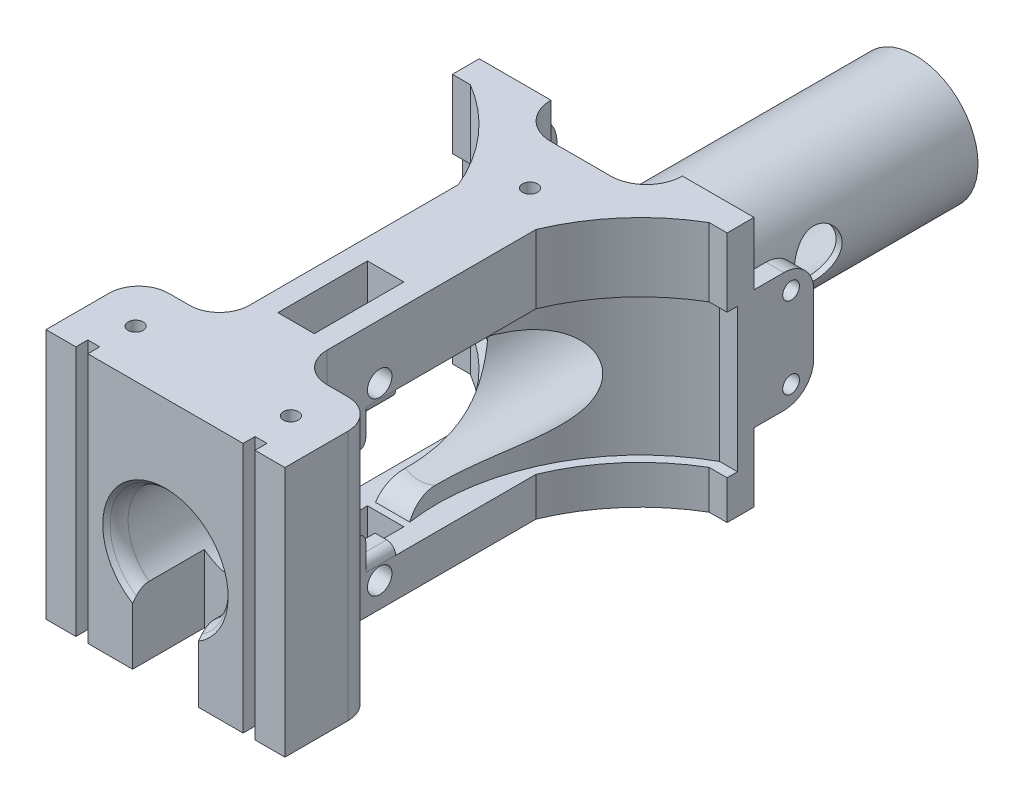
SolidWorks part; units mm, degrees
ref_plane "前视基准面" through (0, 0, 0) normal (0, 0, 1) x (1, 0, 0)
ref_plane "上视基准面" through (0, 0, 0) normal (0, 1, 0) x (1, 0, 0)
ref_plane "右视基准面" through (0, 0, 0) normal (1, 0, 0) x (0, 0, -1)
sketch "草图1" plane through (0, 0, 0) normal (0, 0, 1) x (1, 0, 0)
  line L1 (-20, 23.5) -> (20, 23.5)
  line L2 (-20, 23.5) -> (-20, -23.5)
  line L3 (-20, -23.5) -> (20, -23.5)
  line L4 (20, 23.5) -> (20, -23.5)
  line L5 (-20, 23.5) -> (20, -23.5) construction
  line L6 (-20, -23.5) -> (20, 23.5) construction
  point P0 (0, 0)
  dimension "D1" = 47
  dimension "D2" = 40
extrude "凸台-拉伸1" add sketch "草图1" along normal mid plane 65
sketch "草图2" plane through (0, 23.5, 0) normal (0, 1, 0) x (1, 0, 0)
  line L0 (-36.5, 0) -> (36.5, 0) construction
  line L1 (21.9876, 29.0799) -> (51.0124, 29.0799)
  line L2 (6.5, -27.5) -> (6.5, 12.5)
  line L4 (-6.5, 12.5) -> (-6.5, -27.5)
  line L5 (20, -32.5) -> (-20, -32.5) construction
  line L6 (-51.5217, -27.5) -> (-6.5, -27.5)
  line L8 (-48.1731, 29.0799) -> (-21.9876, 29.0799)
  line L9 (6.5, -27.5) -> (53.8205, -27.5)
  circle A0 centre (36.5, 0) radius 30 construction
  circle A1 centre (-36.5, 0) radius 30 construction
  arc A2 (21.9876, 29.0799) -> (6.5, 12.5) centre (36.5, 0) ccw
  arc A3 (-48.1731, 29.0799) -> (-51.5217, -27.5) centre (-36.5, 0) ccw
  arc A4 (53.8205, -27.5) -> (51.0124, 29.0799) centre (36.5, 0) ccw
  arc A5 (-6.5, 12.5) -> (-21.9876, 29.0799) centre (-36.5, 0) ccw
  point P3 (0, 0)
  dimension "D2" = 60
  dimension "D3" = 65
  dimension "D1" = 73
  dimension "D4" = 5
extrude "切除-拉伸1" cut sketch "草图2" against normal through all
sketch "草图3" plane through (0, 0, 32.5) normal (0, 0, 1) x (1, 0, 0)
  circle A0 centre (0, 0) radius 9
  dimension "D1" = 18
extrude "切除-拉伸2" cut sketch "草图3" against normal through all
sketch "草图4" plane through (0, 0, 0) normal (0, 1, 0) x (1, 0, 0)
  line L1 (56.4937, -27.5) -> (16.5063, -27.5)
  line L2 (-20, -27.5) -> (-6.5, -27.5) construction
  line L3 (52.5, 30) -> (20.5, 30)
  line L5 (-20.5, 30) -> (-52.5, 30)
  line L6 (-16.5063, -27.5) -> (-56.4937, -27.5)
  arc A1 (56.4937, -27.5) -> (52.5, 30) centre (36.5, 0) ccw
  arc A2 (-52.5, 30) -> (-56.4937, -27.5) centre (-36.5, 0) ccw
  arc A3 (-16.5063, -27.5) -> (-20.5, 30) centre (-36.5, 0) ccw
  arc A4 (20.5, 30) -> (16.5063, -27.5) centre (36.5, 0) ccw
  point P8 (36.5, 0)
  point P12 (-36.5, 0)
  dimension "D2" = 34
  dimension "D3" = 34
  dimension "D1" = 73
  dimension "D4" = 36.5
  dimension "D5" = 30
extrude "切除-拉伸3" cut sketch "草图4" against normal mid plane 24
sketch "草图7" plane through (-6.5, 0, 0) normal (-1, 0, 0) x (0, 0, 1)
  circle A1 centre (13.6704, 14.3) radius 2.05
  dimension "D1" = 13.6704
  dimension "D2" = 4.1
  dimension "D3" = 13.6704
  dimension "D4" = 14.3
extrude "切除-拉伸5" cut sketch "草图7" against normal through all
mirror "镜向1" about plane through (0, 0, 0) normal (0, 1, 0) of "切除-拉伸5"
sketch "草图9" plane through (6.5, 0, 0) normal (1, 0, 0) x (0, 0, -1)
  line L0 (-16, -12) -> (12.5, -12) construction
  line L1 (-16, 12) -> (-5, 12)
  line L2 (-16, 12) -> (-16, -12)
  line L3 (-16, -12) -> (-5, -12)
  line L4 (-5, 12) -> (-5, -12)
  line L5 (29.7279, -12) -> (-16, -12) construction
  dimension "D1" = 11
extrude "切除-拉伸7" cut sketch "草图9" against normal through all
sketch "草图10" plane through (0, 0, -32.5) normal (0, 0, -1) x (-1, 0, 0)
  circle A0 centre (0, 0) radius 9.5
  dimension "D1" = 19
extrude "切除-拉伸8" cut sketch "草图10" against normal up to next
sketch "草图12" plane through (0, 23.5, 0) normal (0, 1, 0) x (1, 0, 0)
  line L0 (20, -32.5) -> (-20, -32.5) construction
  line L1 (-3.05, -6.17) -> (3.05, -6.17)
  line L2 (-3.05, -6.17) -> (-3.05, -21.17)
  line L3 (-3.05, -21.17) -> (3.05, -21.17)
  line L4 (3.05, -6.17) -> (3.05, -21.17)
  line L5 (-3.05, -6.17) -> (3.05, -21.17) construction
  line L6 (-3.05, -21.17) -> (3.05, -6.17) construction
  point P0 (0, -13.67)
  dimension "D1" = 18.83
  dimension "D2" = 15
  dimension "D3" = 6.1
extrude "切除-拉伸9" cut sketch "草图12" against normal through all
fillet "圆角4" radius 1 4 edges at (-4.9049, 7.546, 16) (4.9049, 7.546, 16) (4.9049, -7.546, 16) (-4.9049, -7.546, 16)
fillet "圆角5" radius 5 2 edges at (0, -9.5, 5) (0, 9.5, 5)
sketch "草图13" plane through (0, 0, 32.5) normal (0, 0, 1) x (1, 0, 0)
  line L4 (20, -23.5) -> (20, 23.5)
  line L5 (20, 23.5) -> (-20, 23.5)
  line L6 (-20, 23.5) -> (-20, -23.5)
  line L7 (-20, -23.5) -> (20, -23.5)
  line L8 (20, -23.5) -> (20, 23.5)
  line L9 (20, 23.5) -> (-20, 23.5)
  line L10 (-20, 23.5) -> (-20, -23.5)
  line L11 (-20, -23.5) -> (20, -23.5)
  circle A0 centre (0, 0) radius 9 construction
  circle A1 centre (0, 0) radius 9
  dimension "D1" = 0
extrude "凸台-拉伸2" add sketch "草图13" along normal blind 10.54
sketch "草图14" plane through (0, 0, 43.04) normal (0, 0, 1) x (1, 0, 0)
  line L0 (0, 0) -> (0, 30.6084) construction
  line L1 (14, -23.5) -> (14, 23.5) construction
  line L4 (15, -23.5) -> (15, 23.5)
  line L6 (13, -23.5) -> (13, 23.5)
  line L7 (13, 23.5) -> (15, 23.5)
  line L8 (20, 23.5) -> (-20, 23.5) construction
  line L9 (13, -23.5) -> (15, -23.5)
  line L10 (-20, -23.5) -> (20, -23.5) construction
  line L13 (15, 0) -> (15, 30.6084) construction
  line L14 (14, 0) -> (14, 30.6084) construction
  line L15 (13, 0) -> (13, 30.6084) construction
  dimension "D2" = 2
  dimension "D3" = 1
  dimension "D1" = 14
extrude "切除-拉伸10" cut sketch "草图14" against normal blind 2
mirror "镜向2" about plane through (0, 0, 0) normal (1, 0, 0) of "切除-拉伸10"
sketch "草图15" plane through (0, 0, 43.04) normal (0, 0, 1) x (1, 0, 0)
  line L0 (-20, -23.5) -> (-15, -23.5) construction
  line L1 (-20, -23.5) -> (20, -23.5)
  line L2 (-20, -23.5) -> (-20, -18.7)
  line L3 (-20, -18.7) -> (20, -18.7)
  line L4 (20, -23.5) -> (20, -18.7)
  line L5 (-20, 23.5) -> (-20, -23.5) construction
  line L6 (20, -23.5) -> (20, 23.5) construction
  dimension "D1" = 4.8
extrude "切除-拉伸11" cut sketch "草图15" against normal through all
sketch "草图16" plane through (0, -18.7, 0) normal (0, -1, 0) x (1, 0, 0)
  line L0 (13, 43.04) -> (-13, 43.04) construction
  line L1 (-5.5, 43.04) -> (5.5, 43.04)
  line L2 (-5.5, 43.04) -> (-5.5, 31.04)
  line L3 (-5.5, 31.04) -> (5.5, 31.04)
  line L4 (5.5, 43.04) -> (5.5, 31.04)
  line L5 (-5.5, 43.04) -> (5.5, 31.04) construction
  line L6 (-5.5, 31.04) -> (5.5, 43.04) construction
  point P0 (0, 37.04)
  dimension "D1" = 11
  dimension "D2" = 12
extrude "切除-拉伸12" cut sketch "草图16" against normal up to surface (11.5761 mm away) up to face at (0, 0, 20.6675)
sketch "草图17" plane through (0, -18.7, 0) normal (0, -1, 0) x (1, 0, 0)
  line L0 (10, 37.04) -> (-10, 37.04) construction
  line L2 (9, 43.04) -> (-9, 43.04) construction
  circle A0 centre (-10, 37.04) radius 1.25
  circle A1 centre (10, 37.04) radius 1.25
  point P2 (0, 37.04)
  dimension "D3" = 2.5
  dimension "D1" = 20
  dimension "D2" = 6
extrude "切除-拉伸13" cut sketch "草图17" against normal blind 15
cosmetic thread "装饰螺纹线5" parameters "D2"=3
cosmetic thread "装饰螺纹线6" parameters "D2"=3
sketch "草图18" plane through (0, 0, 43.04) normal (0, 0, 1) x (1, 0, 0)
  line L0 (0, 0) -> (0, -18.7) construction
  line L1 (-5.5, -18.7) -> (5.5, -18.7) construction
  line L3 (6.5, -12) -> (13.5, -12)
  line L4 (6.5, -12) -> (6.5, -15.2)
  line L5 (6.5, -15.2) -> (13.5, -15.2)
  line L6 (13.5, -12) -> (13.5, -15.2)
  dimension "D1" = 7
  dimension "D2" = 3.2
  dimension "D3" = 6.5
  dimension "D4" = 12
extrude "切除-拉伸14" [suppressed] cut sketch "草图18" against normal blind 38
mirror "镜向3" [suppressed] about plane through (0, 0, 0) normal (1, 0, 0)
fillet "圆角7" radius 5 2 edges at (6.5, -12.4625, 27.5) (-6.5, -12.4625, 27.5)
chamfer "倒角1" distance 1.5 angle 45 1 edges at (0, 9, 43.04)
fillet "圆角8" radius 3 1 edges at (0, 9, 41.54)
chamfer "倒角2" [suppressed] distance 1.5 angle 45
sketch "草图19" plane through (0, 12, 0) normal (0, -1, 0) x (1, 0, 0)
  line L0 (-3.05, 16) -> (-6.5, 16)
  line L1 (-6.5, 16) -> (-6.5, 11)
  line L2 (-6.5, -12.5) -> (-6.5, 22.5) construction
  line L3 (-6.5, 11) -> (-3.05, 11)
  line L4 (-3.05, 21.17) -> (-3.05, 6.17) construction
  line L5 (-3.05, 11) -> (-3.05, 16)
  line L6 (3.05, 16) -> (6.5, 16)
  line L7 (6.5, 22.5) -> (6.5, -12.5) construction
  line L8 (6.5, 16) -> (6.5, 11)
  line L9 (6.5, 11) -> (3.05, 11)
  line L10 (3.05, 6.17) -> (3.05, 21.17) construction
  line L11 (3.05, 11) -> (3.05, 16)
  dimension "D1" = 5
extrude "凸台-拉伸3" add sketch "草图19" along normal blind 1.5
mirror "镜向8" about plane through (0, 0, 0) normal (0, 1, 0) of "凸台-拉伸3"
fillet "圆角9" [suppressed] radius 10
fillet "圆角10" radius 1.5 4 edges at (-6.5, 10.5, 13.5) (6.5, 10.5, 13.5) (-6.5, -10.5, 13.5) (6.5, -10.5, 13.5)
sketch "草图20" plane through (-20, 0, 0) normal (-1, 0, 0) x (0, 0, 1)
  line L0 (-32.5, 23.5) -> (-32.5, -18.7) construction
  line L1 (-37.5, 12.9983) -> (-32.5, 12.9983)
  line L2 (-42.5, 7.9983) -> (-42.5, -2.0017)
  line L3 (-37.5, -7.0017) -> (-32.5, -7.0017)
  line L4 (-32.5, 12.9983) -> (-32.5, -7.0017)
  line L5 (-38.7, 9.8) -> (-38.7, -3.8) construction
  line L14 (-32.5, 23.5) -> (-32.5, -18.7)
  line L15 (-32.5, -18.7) -> (-28, -18.7)
  line L16 (-28, -18.7) -> (-28, -12)
  line L17 (-28, -12) -> (-29.7279, -12)
  line L18 (-29.7279, -12) -> (-29.7279, 12)
  line L19 (-29.7279, 12) -> (-28, 12)
  line L20 (-28, 12) -> (-28, 23.5)
  line L21 (-28, 23.5) -> (-32.5, 23.5)
  line L22 (-32.5, 23.5) -> (-32.5, -18.7)
  line L23 (-32.5, -18.7) -> (-28, -18.7)
  line L24 (-28, -18.7) -> (-28, -12)
  line L25 (-28, -12) -> (-29.7279, -12)
  line L26 (-29.7279, -12) -> (-29.7279, 12)
  line L27 (-29.7279, 12) -> (-28, 12)
  line L28 (-28, 12) -> (-28, 23.5)
  line L29 (-28, 23.5) -> (-32.5, 23.5)
  circle A0 centre (-38.7, -3.8) radius 1.4
  circle A1 centre (-38.7, 9.8) radius 1.4
  arc A2 (-37.5, 12.9983) -> (-42.5, 7.9983) centre (-37.5, 7.9983) ccw
  arc A3 (-42.5, -2.0017) -> (-37.5, -7.0017) centre (-37.5, -2.0017) ccw
  point P10 (-32.5, 2.9983)
  point P15 (-42.5, 12.9983)
  point P18 (-42.5, -7.0017)
  line M2 (-32.5, 23.5) -> (-32.5, -18.7)
  line M3 (-32.5, -18.7) -> (-28, -18.7)
  line M4 (-28, -18.7) -> (-28, -12)
  line M5 (-28, -12) -> (-29.7279, -12)
  line M6 (-29.7279, -12) -> (-29.7279, 12)
  line M7 (-29.7279, 12) -> (-28, 12)
  line M8 (-28, 12) -> (-28, 23.5)
  line M9 (-28, 23.5) -> (-32.5, 23.5)
  dimension "D1" = 2.8
  dimension "D5" = 9.8
  dimension "D8" = 5
  dimension "D2" = 2.9983
  dimension "D3" = 38.7
  dimension "D4" = 13.6
  dimension "D6" = 20
  dimension "D7" = 10
  dimension "D9" = 0
extrude "凸台-拉伸5" add sketch "草图20" along normal blind 3 contours M9 M2 M3 M4 M5 M6 M7 M8 | L2 A3 L3 L1 A2 A1 A0 M2 region at (-20, 2.9981, -37.181) region at (-20, 3.0705, -30.6372)
mirror "镜向9" about plane through (0, 0, 0) normal (1, 0, 0) of "凸台-拉伸5"
sketch "草图21" plane through (0, 0, -32.5) normal (0, 0, -1) x (-1, 0, 0)
  circle A0 centre (0, 0) radius 9.5
  circle A1 centre (0, 0) radius 10.5
  dimension "D1" = 21
  dimension "D2" = 19
extrude "凸台-拉伸6" add sketch "草图21" along normal up to surface (10 mm away) up to face at (21.5, 2.9983, -42.5)
sketch "草图22" plane through (20, 0, 0) normal (1, 0, 0) x (0, 0, -1)
  line L0 (-43.04, 23.5) -> (-27.5, 23.5) construction
  line L1 (-38.04, 18.5) -> (-32.04, 18.5)
  line L2 (-38.04, 18.5) -> (-38.04, 15.3)
  line L3 (-38.04, 15.3) -> (-32.04, 15.3)
  line L4 (-32.04, 18.5) -> (-32.04, 15.3)
  line L5 (-43.04, -18.7) -> (-43.04, 23.5) construction
  dimension "D1" = 6
  dimension "D2" = 3.2
  dimension "D3" = 5
  dimension "D4" = 5
extrude "切除-拉伸15" [suppressed] cut sketch "草图22" against normal through all
sketch "草图23" plane through (0, 23.5, 0) normal (0, 1, 0) x (1, 0, 0)
  line L0 (-13, -35.04) -> (13, -35.04) construction
  line L1 (20, -43.04) -> (15, -43.04) construction
  circle A0 centre (13, -35.04) radius 1.25
  circle A1 centre (-13, -35.04) radius 1.25
  point P2 (0, -35.04)
  dimension "D3" = 2.5
  dimension "D1" = 26
  dimension "D2" = 8
extrude "切除-拉伸16" cut sketch "草图23" against normal blind 10
cosmetic thread "装饰螺纹线1" parameters "D2"=3
cosmetic thread "装饰螺纹线2" parameters "D2"=3
sketch "草图26" plane through (0, 0, -32.5) normal (0, 0, -1) x (-1, 0, 0)
  line L0 (-23, -18.7) -> (23, -18.7) construction
  line L1 (-3, -12.5) -> (3, -12.5)
  line L2 (-3, -12.5) -> (-3, -15.7)
  line L3 (-3, -15.7) -> (3, -15.7)
  line L4 (3, -12.5) -> (3, -15.7)
  line L5 (-3, -12.5) -> (3, -15.7) construction
  line L6 (-3, -15.7) -> (3, -12.5) construction
  point P0 (0, -14.1)
  dimension "D1" = 3.2
  dimension "D2" = 6
  dimension "D3" = 3
extrude "切除-拉伸19" [suppressed] cut sketch "草图26" against normal blind 10
sketch "草图27" plane through (0, -18.7, 0) normal (0, -1, 0) x (1, 0, 0)
  line L0 (23, -32.5) -> (-23, -32.5) construction
  circle A0 centre (0, -27.5) radius 1.25
  dimension "D1" = 2.5
  dimension "D2" = 5
extrude "切除-拉伸20" cut sketch "草图27" against normal blind 8
cosmetic thread "装饰螺纹线4" parameters "D2"=3
fillet "圆角11" radius 5 2 edges at (-20, 2.4, 27.5) (20, 2.4, 27.5)
sketch "草图28" plane through (0, 23.5, 0) normal (0, 1, 0) x (1, 0, 0)
  line L1 (-5, 32.5) -> (5, 32.5) construction
  line L2 (23, 32.5) -> (-23, 32.5) construction
  line L3 (-5, 38.5) -> (5, 38.5)
  line L4 (-5, 26.5) -> (5, 26.5)
  arc A1 (-5, 38.5) -> (-5, 26.5) centre (-5, 32.5) ccw
  arc A2 (5, 26.5) -> (5, 38.5) centre (5, 32.5) ccw
  point P4 (0, 32.5)
  dimension "D1" = 10
  dimension "D2" = 6
extrude "切除-拉伸21" cut sketch "草图28" against normal blind 10
sketch "草图30" [suppressed] plane through (0, 0, 0) normal (1, 0, 0) x (0, 0, -1)
  line L0 (-32.5, 18.5) -> (-38.04, 18.5) construction
  line L1 (15, 18.5) -> (21, 18.5)
  line L2 (15, 18.5) -> (15, 15.3)
  line L3 (15, 15.3) -> (21, 15.3)
  line L4 (21, 18.5) -> (21, 15.3)
  dimension "D1" = 3.2
  dimension "D2" = 6
  dimension "D3" = 15
extrude "切除-拉伸22" [suppressed] cut sketch "草图30" against normal mid plane 55
sketch "草图31" plane through (0, 23.5, 0) normal (0, 1, 0) x (1, 0, 0)
  circle A0 centre (0, 18) radius 1.25
  dimension "D1" = 2.5
  dimension "D2" = 18
extrude "切除-拉伸23" cut sketch "草图31" against normal blind 11
cosmetic thread "装饰螺纹线3" parameters "D2"=3
sketch "草图32" plane through (0, -18.7, 0) normal (0, -1, 0) x (1, 0, 0)
  line L24 (-20, 43.04) -> (-20, 32.5)
  line L25 (-15, 27.5) -> (-11.5, 27.5)
  line L26 (-6.5, 22.5) -> (-6.5, -12.5)
  line L27 (-20, -28) -> (-23, -28)
  line L28 (-23, -28) -> (-23, -32.5)
  line L29 (-23, -32.5) -> (23, -32.5)
  line L30 (23, -32.5) -> (23, -28)
  line L31 (23, -28) -> (20, -28)
  line L32 (6.5, -12.5) -> (6.5, 22.5)
  line L33 (11.5, 27.5) -> (15, 27.5)
  line L34 (20, 32.5) -> (20, 43.04)
  line L35 (20, 43.04) -> (15, 43.04)
  line L36 (15, 43.04) -> (15, 41.04)
  line L37 (15, 41.04) -> (13, 41.04)
  line L38 (13, 41.04) -> (13, 43.04)
  line L39 (13, 43.04) -> (5.5, 43.04)
  line L40 (5.5, 43.04) -> (5.5, 31.04)
  line L41 (5.5, 31.04) -> (-5.5, 31.04)
  line L42 (-5.5, 31.04) -> (-5.5, 43.04)
  line L43 (-5.5, 43.04) -> (-13, 43.04)
  line L44 (-13, 43.04) -> (-13, 41.04)
  line L45 (-13, 41.04) -> (-15, 41.04)
  line L46 (-15, 41.04) -> (-15, 43.04)
  line L47 (-15, 43.04) -> (-20, 43.04)
  line L48 (-20, 43.04) -> (-20, 32.5)
  line L49 (-15, 27.5) -> (-11.5, 27.5)
  line L50 (-6.5, 22.5) -> (-6.5, -12.5)
  line L51 (-20, -28) -> (-23, -28)
  line L52 (-23, -28) -> (-23, -32.5)
  line L53 (-23, -32.5) -> (23, -32.5)
  line L54 (23, -32.5) -> (23, -28)
  line L55 (23, -28) -> (20, -28)
  line L56 (6.5, -12.5) -> (6.5, 22.5)
  line L57 (11.5, 27.5) -> (15, 27.5)
  line L58 (20, 32.5) -> (20, 43.04)
  line L59 (20, 43.04) -> (15, 43.04)
  line L60 (15, 43.04) -> (15, 41.04)
  line L61 (15, 41.04) -> (13, 41.04)
  line L62 (13, 41.04) -> (13, 43.04)
  line L63 (13, 43.04) -> (5.5, 43.04)
  line L64 (5.5, 43.04) -> (5.5, 31.04)
  line L65 (5.5, 31.04) -> (-5.5, 31.04)
  line L66 (-5.5, 31.04) -> (-5.5, 43.04)
  line L67 (-5.5, 43.04) -> (-13, 43.04)
  line L68 (-13, 43.04) -> (-13, 41.04)
  line L69 (-13, 41.04) -> (-15, 41.04)
  line L70 (-15, 41.04) -> (-15, 43.04)
  line L71 (-15, 43.04) -> (-20, 43.04)
  arc A6 (-20, 32.5) -> (-15, 27.5) centre (-15, 32.5) ccw
  arc A7 (-6.5, 22.5) -> (-11.5, 27.5) centre (-11.5, 22.5) ccw
  arc A8 (-20, -28) -> (-6.5, -12.5) centre (-36.5, 0) ccw
  arc A9 (6.5, -12.5) -> (20, -28) centre (36.5, 0) ccw
  arc A10 (11.5, 27.5) -> (6.5, 22.5) centre (11.5, 22.5) ccw
  arc A11 (15, 27.5) -> (20, 32.5) centre (15, 32.5) ccw
  arc A12 (-20, 32.5) -> (-15, 27.5) centre (-15, 32.5) ccw
  arc A13 (-6.5, 22.5) -> (-11.5, 27.5) centre (-11.5, 22.5) ccw
  arc A14 (-20, -28) -> (-6.5, -12.5) centre (-36.5, 0) ccw
  arc A15 (6.5, -12.5) -> (20, -28) centre (36.5, 0) ccw
  arc A16 (11.5, 27.5) -> (6.5, 22.5) centre (11.5, 22.5) ccw
  arc A17 (15, 27.5) -> (20, 32.5) centre (15, 32.5) ccw
  dimension "D1" = 0
extrude "切除-拉伸24" cut sketch "草图32" against normal blind 0.2
sketch "草图33" plane through (0, 0, -32.5) normal (0, 0, -1) x (-1, 0, 0)
  circle A0 centre (0, 0) radius 10.5
  circle A1 centre (0, 0) radius 9.5
  dimension "D1" = 19
  dimension "D2" = 21
extrude "凸台-拉伸7" add sketch "草图33" along normal blind 50
sketch "草图34" plane through (0, 0, 0) normal (1, 0, 0) x (0, 0, -1)
  line L0 (32.5, 23.5) -> (32.5, 12.9983) construction
  circle A0 centre (55.75, 0) radius 4
  dimension "D1" = 8
  dimension "D2" = 23.25
extrude "切除-拉伸25" cut sketch "草图34" against normal through all both and the other way through all
